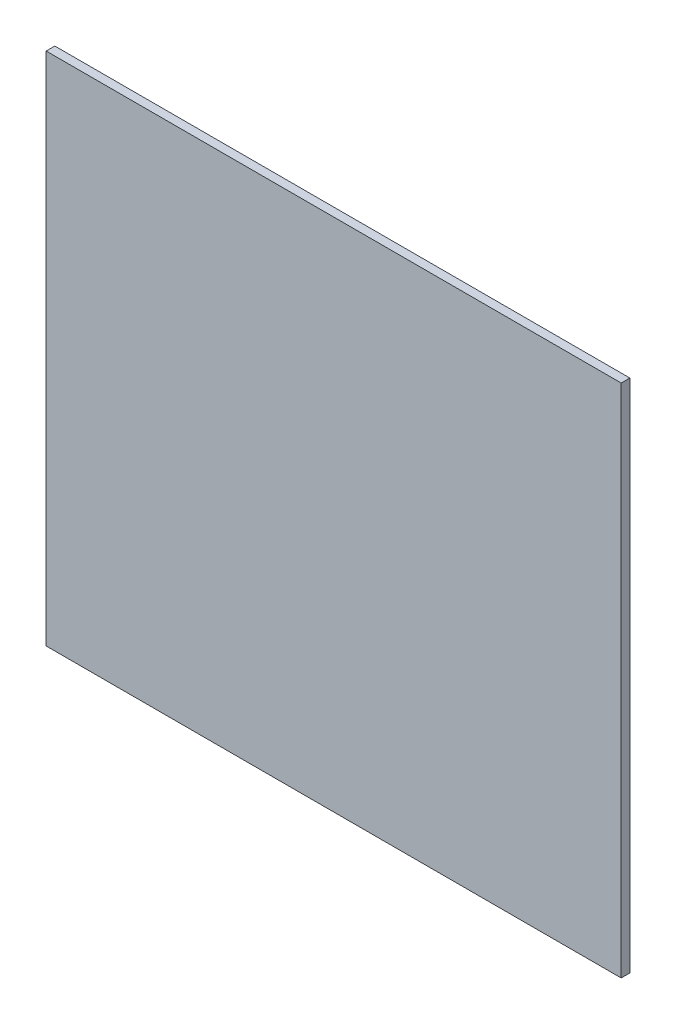
SolidWorks part; units mm, degrees
ref_plane "Plan de face" through (0, 0, 0) normal (0, 0, 1) x (1, 0, 0)
ref_plane "Plan de dessus" through (0, 0, 0) normal (0, 1, 0) x (1, 0, 0)
ref_plane "Plan de droite" through (0, 0, 0) normal (1, 0, 0) x (0, 0, -1)
sketch "Esquisse1" plane through (0, 0, 0) normal (0, 0, 1) x (1, 0, 0)
  line L1 (-49.1302, 219.1251) -> (229.7698, 219.1251)
  line L2 (-49.1302, 219.1251) -> (-49.1302, -30.7749)
  line L3 (-49.1302, -30.7749) -> (229.7698, -30.7749)
  line L4 (229.7698, 219.1251) -> (229.7698, -30.7749)
  dimension "D1" = 249.9
  dimension "D2" = 278.9
extrude "Boss.-Extru.1" add sketch "Esquisse1" along normal blind 4.2
